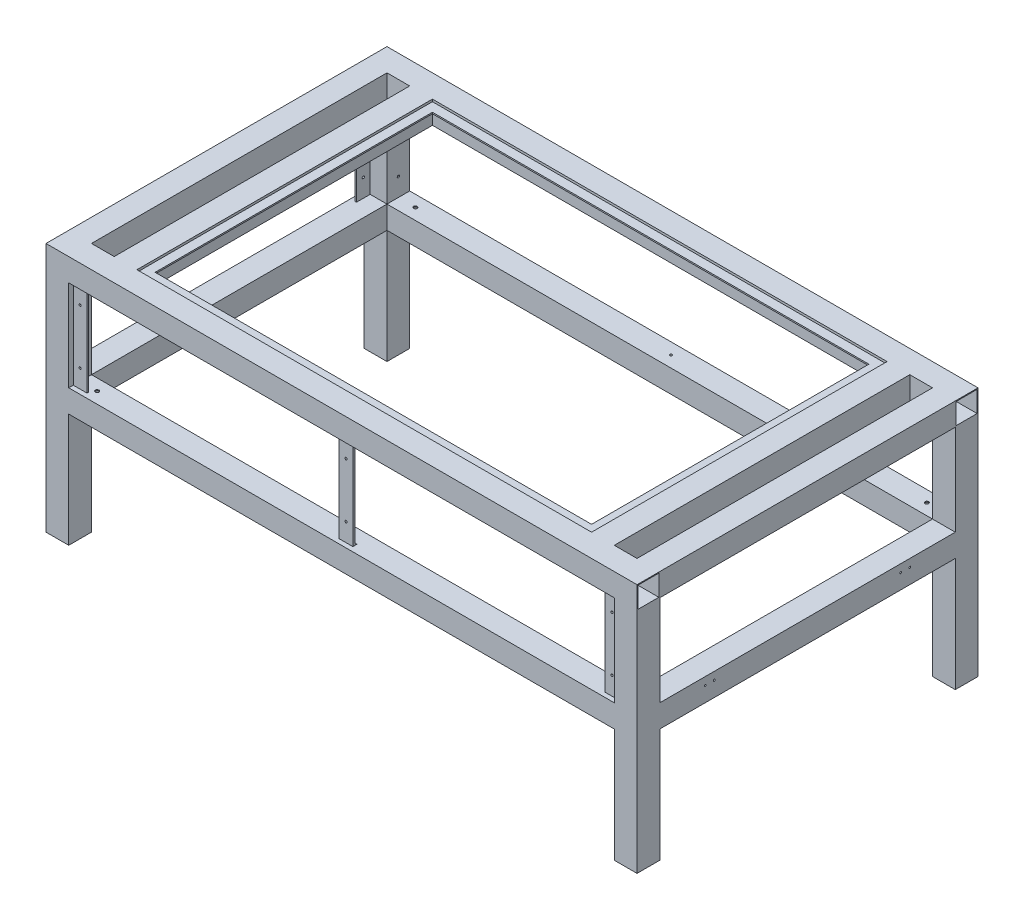
SolidWorks part; units mm, degrees
ref_plane "Plan de face" through (0, 0, 0) normal (0, 0, 1) x (1, 0, 0)
ref_plane "Plan de dessus" through (0, 0, 0) normal (0, 1, 0) x (1, 0, 0)
ref_plane "Plan de droite" through (0, 0, 0) normal (1, 0, 0) x (0, 0, -1)
sketch "Esquisse1" plane through (0, 0, 0) normal (0, 1, 0) x (1, 0, 0)
  line L1 (0, 0) -> (1300, 0)
  line L2 (0, 0) -> (0, 750)
  line L3 (0, 750) -> (1300, 750)
  line L4 (1300, 0) -> (1300, 750)
  line L5 (50, 700) -> (1250, 700)
  line L6 (50, 700) -> (50, 50)
  line L7 (50, 50) -> (1250, 50)
  line L8 (1250, 700) -> (1250, 50)
  dimension "D1" = 1300
  dimension "D2" = 750
  dimension "D3" = 50
  dimension "D4" = 50
  dimension "D5" = 50
  dimension "D6" = 50
extrude "Boss.-Extru.1" add sketch "Esquisse1" against normal blind 550
sketch "Esquisse2" plane through (0, 0, 0) normal (0, 0, 1) x (1, 0, 0)
  line L0 (0, 0) -> (1300, 0) construction
  line L1 (50, -50) -> (1250, -50)
  line L2 (50, -50) -> (50, -250)
  line L3 (50, -250) -> (1250, -250)
  line L4 (1250, -50) -> (1250, -250)
  line L5 (50, -300) -> (1250, -300)
  line L6 (50, -300) -> (50, -550)
  line L7 (50, -550) -> (1250, -550)
  line L8 (1250, -300) -> (1250, -550)
  line L9 (0, -550) -> (1300, -550) construction
  line L10 (1300, -550) -> (1300, 0) construction
  line L11 (0, -550) -> (0, 0) construction
  point P12 (1250, -425)
  dimension "D1" = 50
  dimension "D2" = 50
  dimension "D3" = 200
  dimension "D4" = 0
  dimension "D5" = 50
  dimension "D6" = 50
  dimension "D7" = 50
  dimension "D8" = 50
extrude "Enlèv. mat.-Extru.1" cut sketch "Esquisse2" against normal through all
sketch "Esquisse3" plane through (0, 0, 0) normal (-1, 0, 0) x (0, 0, 1)
  line L0 (-750, -550) -> (0, -550) construction
  line L1 (-700, -50) -> (-50, -50)
  line L2 (-700, -50) -> (-700, -250)
  line L3 (-700, -250) -> (-50, -250)
  line L4 (-50, -50) -> (-50, -250)
  line L5 (-700, -300) -> (-50, -300)
  line L6 (-700, -300) -> (-700, -550)
  line L7 (-700, -550) -> (-50, -550)
  line L8 (-50, -300) -> (-50, -550)
  line L9 (-750, 0) -> (0, 0) construction
  line L10 (0, -550) -> (0, 0) construction
  line L11 (-750, -550) -> (-750, 0) construction
  dimension "D1" = 50
  dimension "D2" = 50
  dimension "D3" = 50
  dimension "D4" = 50
  dimension "D5" = 50
  dimension "D6" = 200
  dimension "D7" = 50
extrude "Enlèv. mat.-Extru.2" cut sketch "Esquisse3" against normal through all
sketch "Esquisse4" plane through (0, 0, 0) normal (0, 1, 0) x (1, 0, 0)
  line L0 (1250, 700) -> (50, 700) construction
  line L1 (100, 700) -> (150, 700)
  line L2 (100, 700) -> (100, 50)
  line L3 (100, 50) -> (150, 50)
  line L4 (150, 700) -> (150, 50)
  line L5 (50, 50) -> (1250, 50) construction
  line L6 (50, 700) -> (50, 50) construction
  line L7 (1150, 700) -> (1200, 700)
  line L8 (1150, 700) -> (1150, 50)
  line L9 (1150, 50) -> (1200, 50)
  line L10 (1200, 700) -> (1200, 50)
  line L11 (1250, 50) -> (1250, 700) construction
  dimension "D1" = 50
  dimension "D2" = 50
  dimension "D3" = 50
  dimension "D4" = 50
extrude "Boss.-Extru.2" add sketch "Esquisse4" against normal blind 50 separate body
sketch "Esquisse18" plane through (0, -250, 0) normal (0, 1, 0) x (1, 0, 0)
  line L0 (50, 0) -> (1250, 0) construction
  line L1 (50, 750) -> (1250, 750) construction
  line L2 (1250, 750) -> (1250, 700) construction
  line L3 (50, 750) -> (50, 700) construction
  line L4 (1250, 50) -> (1250, 0) construction
  line L5 (50, 50) -> (50, 0) construction
  circle A0 centre (1212.5, 25) radius 4
  circle A1 centre (87.5, 25) radius 4
  circle A2 centre (87.5, 725) radius 4
  circle A3 centre (1212.5, 725) radius 4
  dimension "D1" = 8
  dimension "D2" = 8
  dimension "D3" = 8
  dimension "D4" = 8
  dimension "D5" = 1125
  dimension "D6" = 1125
  dimension "D7" = 25
  dimension "D8" = 25
  dimension "D9" = 25
  dimension "D10" = 25
  dimension "D11" = 700
  dimension "D12" = 700
  dimension "D13" = 37.5
  dimension "D14" = 37.5
  dimension "D15" = 37.5
  dimension "D16" = 37.5
extrude "Enlèv. mat.-Extru.5" cut sketch "Esquisse18" against normal blind 80
sketch "Esquisse19" plane through (0, -300, 0) normal (0, -1, 0) x (-1, 0, 0)
  circle A0 centre (-1212.5, 725) radius 15
  circle A1 centre (-87.5, 725) radius 15
  circle A2 centre (-87.5, 25) radius 15
  circle A3 centre (-1212.5, 25) radius 15
  dimension "D1" = 30
  dimension "D2" = 30
  dimension "D3" = 30
  dimension "D4" = 30
extrude "Enlèv. mat.-Extru.6" cut sketch "Esquisse19" against normal blind 48
sketch "Esquisse20" plane through (0, 0, 0) normal (-1, 0, 0) x (0, 0, 1)
  line L0 (-750, 0) -> (0, 0) construction
  line L1 (-2, -2) -> (-48, -2)
  line L2 (-2, -2) -> (-2, -48)
  line L3 (-2, -48) -> (-48, -48)
  line L4 (-48, -2) -> (-48, -48)
  line L5 (-702, -2) -> (-748, -2)
  line L6 (-702, -2) -> (-702, -48)
  line L7 (-702, -48) -> (-748, -48)
  line L8 (-748, -2) -> (-748, -48)
  line L9 (-750, -550) -> (-750, 0) construction
  line L10 (0, -550) -> (0, 0) construction
  dimension "D1" = 2
  dimension "D2" = 2
  dimension "D3" = 46
  dimension "D4" = 46
  dimension "D5" = 2
  dimension "D6" = 46
  dimension "D7" = 46
  dimension "D8" = 2
extrude "Enlèv. mat.-Extru.7" cut sketch "Esquisse20" against normal blind 10000
sketch "Esquisse21" plane through (0, -550, 0) normal (0, -1, 0) x (-1, 0, 0)
  line L0 (0, 0) -> (-50, 0) construction
  line L1 (-1252, 2) -> (-1298, 2)
  line L2 (-1252, 2) -> (-1252, 48)
  line L3 (-1252, 48) -> (-1298, 48)
  line L4 (-1298, 2) -> (-1298, 48)
  line L5 (-1252, 702) -> (-1298, 702)
  line L6 (-1252, 702) -> (-1252, 748)
  line L7 (-1252, 748) -> (-1298, 748)
  line L8 (-1298, 702) -> (-1298, 748)
  line L9 (-2, 702) -> (-48, 702)
  line L10 (-2, 702) -> (-2, 748)
  line L11 (-2, 748) -> (-48, 748)
  line L12 (-48, 702) -> (-48, 748)
  line L13 (-2, 2) -> (-48, 2)
  line L14 (-2, 2) -> (-2, 48)
  line L15 (-2, 48) -> (-48, 48)
  line L16 (-48, 2) -> (-48, 48)
  line L17 (-50, 50) -> (-50, 0) construction
  line L18 (-50, 50) -> (0, 50) construction
  line L19 (-50, 700) -> (0, 700) construction
  line L20 (-50, 750) -> (-50, 700) construction
  line L21 (-1300, 700) -> (-1250, 700) construction
  line L22 (-1300, 700) -> (-1300, 750) construction
  line L23 (-1250, 0) -> (-1300, 0) construction
  line L24 (-1300, 0) -> (-1300, 50) construction
  dimension "D1" = 46
  dimension "D2" = 2
  dimension "D3" = 2
  dimension "D4" = 2
  dimension "D5" = 46
  dimension "D6" = 46
  dimension "D7" = 2
  dimension "D8" = 2
  dimension "D9" = 46
  dimension "D10" = 46
  dimension "D11" = 2
  dimension "D12" = 2
  dimension "D13" = 46
  dimension "D14" = 46
  dimension "D15" = 2
  dimension "D16" = 2
extrude "Enlèv. mat.-Extru.8" cut sketch "Esquisse21" against normal blind 500
sketch "Esquisse22" plane through (0, 0, -50) normal (0, 0, -1) x (-1, 0, 0)
  line L0 (-50, -50) -> (0, -50) construction
  line L1 (-10, -50) -> (-40, -50)
  line L2 (-10, -50) -> (-10, -250)
  line L3 (-10, -250) -> (-40, -250)
  line L4 (-40, -50) -> (-40, -250)
  line L5 (-50, -250) -> (0, -250) construction
  line L6 (0, -250) -> (0, -50) construction
  dimension "D1" = 30
  dimension "D2" = 10
extrude "Boss.-Extru.11" add sketch "Esquisse22" along normal blind 3
sketch "Esquisse23" plane through (10, 0, 0) normal (-1, 0, 0) x (0, 0, 1)
  line L2 (-50, -250) -> (-80, -250)
  line L3 (-50, -250) -> (-50, -50)
  line L4 (-50, -50) -> (-80, -50)
  line L5 (-80, -250) -> (-80, -50)
  line L6 (-53, -50) -> (-50, -50) construction
  circle A0 centre (-65, -90) radius 2.5
  circle A1 centre (-65, -210) radius 2.5
  dimension "D2" = 5
  dimension "D3" = 5
  dimension "D1" = 30
  dimension "D4" = 0
  dimension "D5" = 15
  dimension "D6" = 15
  dimension "D7" = 40
  dimension "D8" = 40
extrude "Boss.-Extru.12" add sketch "Esquisse23" against normal blind 3
ref_plane "Plan1" through (0, 0, -375) normal (0, 0, 1) x (1, 0, 0)
ref_plane "Plan2" through (650, 0, 0) normal (-1, 0, 0) x (0, 0, 1)
ref_plane "Plan4" through (137.5, 0, 137.5) normal (0.7071, 0, 0.7071) x (0.7071, 0, -0.7071)
ref_plane "Plan5" through (0, 0, 0) normal (-0.7071, 0, -0.7071) x (-0.7071, 0, 0.7071)
mirror "Symétrie3" about plane through (0, 0, 0) normal (-0.7071, 0, -0.7071) of "Boss.-Extru.11", "Boss.-Extru.12"
sketch "Esquisse25" plane through (0, 0, -50) normal (0, 0, -1) x (-1, 0, 0)
  line L0 (-150, -50) -> (-150, 0) construction
  line L1 (-150, -5) -> (-1150, -5)
  line L2 (-150, -5) -> (-150, -25)
  line L3 (-150, -25) -> (-1150, -25)
  line L4 (-1150, -5) -> (-1150, -25)
  line L5 (-1150, -50) -> (-1150, 0) construction
  line L6 (-50, 0) -> (-1250, 0) construction
  dimension "D1" = 5
  dimension "D2" = 20
extrude "Boss.-Extru.14" add sketch "Esquisse25" along normal blind 3
sketch "Esquisse26" plane through (0, -5, 0) normal (0, 1, 0) x (1, 0, 0)
  line L0 (150, 50) -> (150, 700) construction
  line L1 (1150, 50) -> (150, 50)
  line L2 (1150, 50) -> (1150, 70)
  line L3 (1150, 70) -> (150, 70)
  line L4 (150, 50) -> (150, 70)
  dimension "D1" = 0
  dimension "D2" = 20
extrude "Boss.-Extru.15" add sketch "Esquisse26" against normal blind 3
mirror "Symétrie6" about plane through (0, 0, -375) normal (0, 0, 1) of "Boss.-Extru.15", "Boss.-Extru.14"
sketch "Esquisse27" plane through (1150, 0, 0) normal (-1, 0, 0) x (0, 0, 1)
  line L1 (-50, -5) -> (-700, -5)
  line L2 (-50, -5) -> (-50, -25)
  line L3 (-50, -25) -> (-700, -25)
  line L4 (-700, -5) -> (-700, -25)
extrude "Boss.-Extru.16" add sketch "Esquisse27" along normal blind 3
sketch "Esquisse28" plane through (0, -5, 0) normal (0, 1, 0) x (1, 0, 0)
  line L0 (150, 700) -> (1150, 700) construction
  line L1 (1150, 50) -> (1130, 50)
  line L2 (1150, 50) -> (1150, 700)
  line L3 (1150, 700) -> (1130, 700)
  line L4 (1130, 50) -> (1130, 700)
  dimension "D1" = 20
extrude "Boss.-Extru.17" add sketch "Esquisse28" against normal blind 3
mirror "Symétrie7" about plane through (650, 0, 0) normal (-1, 0, 0) of "Boss.-Extru.16", "Boss.-Extru.17"
sketch "Esquisse29" plane through (1250, 0, 0) normal (-1, 0, 0) x (0, 0, 1)
  line L0 (-750, -250) -> (-750, -50) construction
  line L1 (-750, -50) -> (-700, -50) construction
  line L2 (-750, -250) -> (-700, -250) construction
  circle A0 centre (-725, -210) radius 2.5
  circle A1 centre (-725, -90) radius 2.5
  dimension "D1" = 5
  dimension "D2" = 5
  dimension "D3" = 25
  dimension "D4" = 25
  dimension "D5" = 40
  dimension "D6" = 40
extrude "Enlèv. mat.-Extru.9" cut sketch "Esquisse29" against normal blind 10
mirror "Symétrie9" about plane through (650, 0, 0) normal (-1, 0, 0) of "Enlèv. mat.-Extru.9"
sketch "Esquisse30" plane through (0, -250, 0) normal (0, 1, 0) x (1, 0, 0)
  line L1 (50, 750) -> (1250, 750) construction
  line L2 (650, 302.5) -> (650, -302.5) construction
  circle A0 centre (650, 725) radius 2.5
  dimension "D1" = 5
  dimension "D2" = 25
  dimension "D3" = 0
extrude "Enlèv. mat.-Extru.10" cut sketch "Esquisse30" against normal blind 15
ref_plane "Plan6" through (0, -150, 0) normal (0, -1, 0) x (-1, 0, 0)
mirror "Symétrie10" about plane through (0, -150, 0) normal (0, -1, 0) of "Enlèv. mat.-Extru.10"
sketch "Esquisse31" plane through (0, -250, 0) normal (0, 1, 0) x (1, 0, 0)
  line L0 (50, 0) -> (1250, 0) construction
  line L1 (635, 15) -> (665, 15)
  line L2 (635, 15) -> (635, 10)
  line L3 (635, 10) -> (665, 10)
  line L4 (665, 15) -> (665, 10)
  line L5 (650, 302.5) -> (650, -302.5) construction
  point P6 (650, 10)
  dimension "D1" = 5
  dimension "D2" = 10
  dimension "D3" = 0
  dimension "D4" = 30
extrude "Boss.-Extru.18" add sketch "Esquisse31" along normal blind 200
fillet "Congé1" radius 5 2 edges at (650, -250, -15) (650, -50, -15)
sketch "Esquisse32" plane through (0, 0, -10) normal (0, 0, 1) x (1, 0, 0)
  line L0 (635, -250) -> (665, -250) construction
  line L1 (635, -50) -> (665, -50) construction
  line L2 (635, -50) -> (635, -250) construction
  circle A0 centre (650, -210) radius 2.5
  circle A1 centre (650, -90) radius 2.5
  dimension "D1" = 5
  dimension "D2" = 5
  dimension "D3" = 40
  dimension "D4" = 40
  dimension "D5" = 15
  dimension "D6" = 15
extrude "Enlèv. mat.-Extru.11" cut sketch "Esquisse32" against normal blind 5
mirror "Symétrie11" about plane through (0, 0, -375) normal (0, 0, 1) of "Boss.-Extru.12"
mirror "Symétrie15" about plane through (650, 0, 0) normal (-1, 0, 0) of "Symétrie3"
sketch "Esquisse33" plane through (1300, 0, 0) normal (1, 0, 0) x (0, 0, -1)
  line L0 (50, -50) -> (700, -50) construction
  line L1 (50, -250) -> (130.649, -250)
  line L2 (50, -250) -> (50, -50)
  line L3 (50, -50) -> (130.649, -50)
  line L4 (130.649, -250) -> (130.649, -50)
extrude "Enlèv. mat.-Extru.12" cut sketch "Esquisse33" against normal blind 78
sketch "Esquisse34" plane through (1300, 0, 0) normal (1, 0, 0) x (0, 0, -1)
  line L0 (50, -250) -> (50, -50) construction
  line L1 (700, -250) -> (50, -250) construction
  circle A0 centre (150, -267) radius 2
  circle A1 centre (170, -267) radius 2
  dimension "D2" = 4
  dimension "D3" = 4
  dimension "D1" = 20
  dimension "D4" = 100
  dimension "D5" = 17
  dimension "D6" = 17
extrude "Enlèv. mat.-Extru.13" cut sketch "Esquisse34" against normal blind 25
mirror "Symétrie16" about plane through (0, 0, -375) normal (0, 0, 1) of "Enlèv. mat.-Extru.13"
